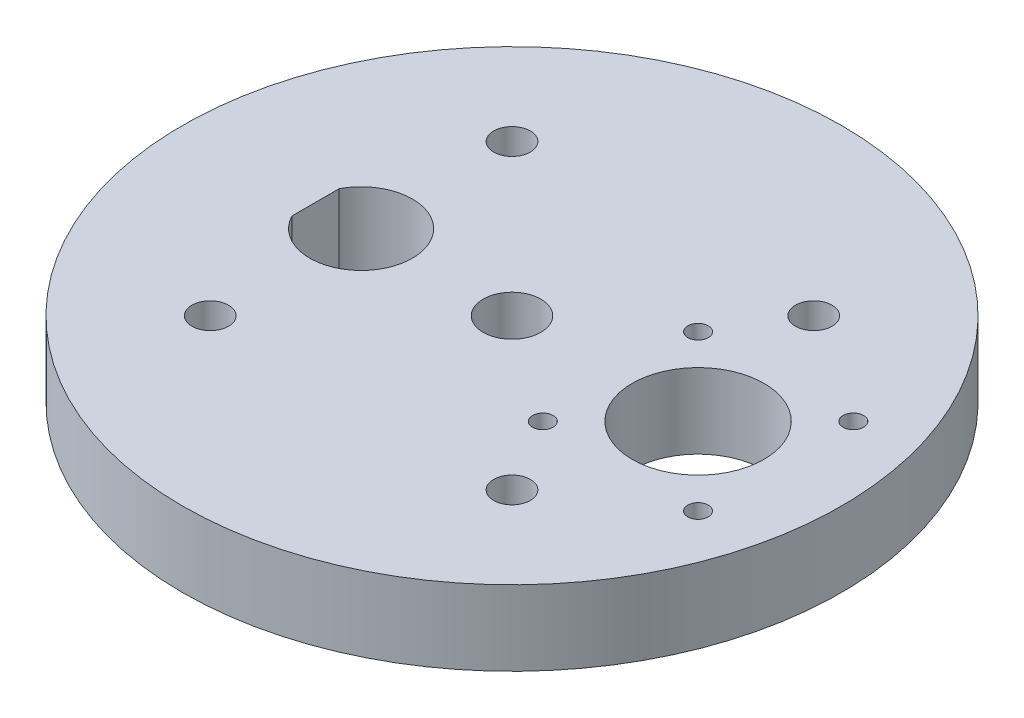
SolidWorks part; units mm, degrees
ref_plane "Front Plane" through (0, 0, 0) normal (0, 0, 1) x (1, 0, 0)
ref_plane "Top Plane" through (0, 0, 0) normal (0, 1, 0) x (1, 0, 0)
ref_plane "Right Plane" through (0, 0, 0) normal (1, 0, 0) x (0, 0, -1)
sketch "Sketch2" plane through (0, 0, 0) normal (0, 1, 0) x (1, 0, 0)
  circle A0 centre (0, 0) radius 57.15
  dimension "D1" = 114.3
extrude "Boss-Extrude1" add sketch "Sketch2" along normal blind 13 contours A0
sketch "Sketch6" plane through (0, 13, 0) normal (0, 1, 0) x (1, 0, 0)
  circle A0 centre (-26.1629, -26.1629) radius 3.175
  circle A1 centre (26.1629, -26.1629) radius 3.175
  circle A2 centre (-26.1629, 26.1631) radius 3.175
  circle A3 centre (26.1629, 26.1631) radius 3.175
  dimension "D1" = 6.35
  dimension "D2" = 74
  dimension "D3" = 26.1629
  dimension "D4" = 26.1629
  dimension "D5" = 26.1629
extrude "Cut-Extrude1" cut sketch "Sketch6" against normal up to next
sketch "Sketch7" plane through (0, 13, 0) normal (0, 1, 0) x (1, 0, 0)
  circle A0 centre (32, 0.2699) radius 11.43
  circle A3 centre (18.54, -13.1941) radius 1.778
  circle A4 centre (18.54, 13.7299) radius 1.778
  circle A5 centre (45.46, 13.7299) radius 1.778
  circle A6 centre (45.46, -13.1941) radius 1.778
  point P10 (0, 0)
  dimension "D1" = 22.86
  dimension "D2" = 3.556
  dimension "D3" = 3.556
  dimension "D4" = 3.556
  dimension "D5" = 3.556
  dimension "D6" = 13.46
  dimension "D7" = 13.46
  dimension "D8" = 13.46
  dimension "D9" = 13.464
  dimension "D10" = 32
extrude "Cut-Extrude2" cut sketch "Sketch7" against normal through all
sketch "Sketch8" plane through (0, 13, 0) normal (0, 1, 0) x (1, 0, 0)
  line L0 (-34.0629, 4.0988) -> (-34.0629, -4.0988)
  circle A2 centre (0, 0) radius 5
  arc A3 (-34.0629, -4.0988) -> (-34.0629, 4.0988) centre (-26.1629, 0) ccw
  circle A4 centre (-26.1629, 26.1631) radius 3.175 construction
  dimension "D1" = 7.9
  dimension "D2" = 0
  dimension "D3" = 10
  dimension "D4" = 17.8
extrude "Cut-Extrude3" cut sketch "Sketch8" against normal through all
equation "\"width\"=26.1629"
equation "\"D4@Sketch6\"=\"width\""
equation "\"D3@Sketch6\"=\"width\""
equation "\"D5@Sketch6\"=\"width\""
